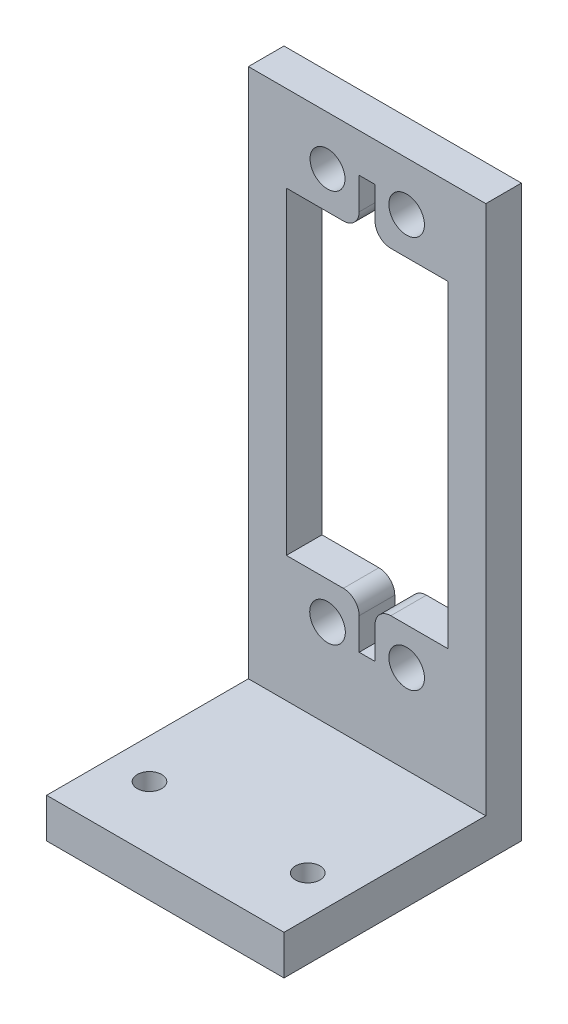
SolidWorks part; units mm, degrees
ref_plane "前视基准面" through (0, 0, 0) normal (0, 0, 1) x (1, 0, 0)
ref_plane "上视基准面" through (0, 0, 0) normal (0, 1, 0) x (1, 0, 0)
ref_plane "右视基准面" through (0, 0, 0) normal (1, 0, 0) x (0, 0, -1)
sketch "草图1" plane through (0, 0, 0) normal (0, 0, 1) x (1, 0, 0)
  line L1 (10.2, -20.1) -> (-10.2, -20.1)
  line L2 (10.2, -20.1) -> (10.2, 20.1)
  line L3 (10.2, 20.1) -> (-10.2, 20.1)
  line L4 (-10.2, -20.1) -> (-10.2, 20.1)
  line L5 (10.2, -20.1) -> (-10.2, 20.1) construction
  line L6 (10.2, 20.1) -> (-10.2, -20.1) construction
  line L7 (15, -31) -> (-15, -31)
  line L8 (15, -31) -> (15, 31)
  line L9 (15, 31) -> (-15, 31)
  line L10 (-15, -31) -> (-15, 31)
  line L11 (15, -31) -> (-15, 31) construction
  line L12 (15, 31) -> (-15, -31) construction
  point P0 (0, 0)
  point P5 (0, 0)
  dimension "D1" = 20.4
  dimension "D2" = 40.2
  dimension "D3" = 30
  dimension "D4" = 62
extrude "凸台-拉伸1" add sketch "草图1" along normal blind 4.5
sketch "草图3" plane through (0, 0, 0) normal (0, 0, -1) x (-1, 0, 0)
  circle A0 centre (-5, -24.8) radius 2.25
  circle A1 centre (5, -24.8) radius 2.25
  circle A2 centre (-5, 24.8) radius 2.25
  circle A3 centre (5, 24.8) radius 2.2065
extrude "切除-拉伸1" cut sketch "草图3" against normal through all
sketch "草图4" plane through (0, 31, 0) normal (0, 1, 0) x (1, 0, 0)
  line L4 (15, 0) -> (-15, 0)
  line L5 (-15, 0) -> (-15, -4.5)
  line L6 (-15, -4.5) -> (15, -4.5)
  line L7 (15, -4.5) -> (15, 0)
  line L8 (15, 0) -> (-15, 0)
  line L9 (-15, 0) -> (-15, -4.5)
  line L10 (-15, -4.5) -> (15, -4.5)
  line L11 (15, -4.5) -> (15, 0)
  dimension "D1" = 0
sketch "草图5" plane through (0, -31, 0) normal (0, -1, 0) x (1, 0, 0)
  line L4 (-15, 0) -> (15, 0)
  line L5 (15, 0) -> (15, 4.5)
  line L6 (15, 4.5) -> (-15, 4.5)
  line L7 (-15, 4.5) -> (-15, 0)
  line L8 (-15, 0) -> (15, 0)
  line L9 (15, 0) -> (15, 4.5)
  line L10 (15, 4.5) -> (-15, 4.5)
  line L11 (-15, 4.5) -> (-15, 0)
  dimension "D1" = 0
extrude "凸台-拉伸3" add sketch "草图5" along normal blind 5
sketch "草图6" plane through (0, -36, 0) normal (0, -1, 0) x (1, 0, 0)
  line L0 (-15, 4.5) -> (-15, 0) construction
  line L1 (15, 0) -> (-15, 0)
  line L2 (15, 0) -> (15, 30)
  line L3 (15, 30) -> (-15, 30)
  line L4 (-15, 0) -> (-15, 30)
  dimension "D1" = 30
extrude "凸台-拉伸4" add sketch "草图6" along normal blind 5
sketch "草图7" plane through (0, -41, 0) normal (0, -1, 0) x (1, 0, 0)
  line L0 (0, 30) -> (0, 22) construction
  line L1 (15, 30) -> (-15, 30) construction
  line L2 (0, 22) -> (10, 22) construction
  circle A0 centre (10, 22) radius 1.55
  circle A1 centre (-10, 22) radius 1.55
  dimension "D1" = 8
  dimension "D3" = 3.1
  dimension "D2" = 10
extrude "切除-拉伸2" cut sketch "草图7" against normal through all
sketch "草图8" plane through (0, 0, 4.5) normal (0, 0, 1) x (1, 0, 0)
  line L0 (0, -20.1) -> (0, -26.5553) construction
  line L1 (-10.2, -20.1) -> (10.2, -20.1) construction
  line L2 (0, 0) -> (13.0244, 0) construction
  line L3 (1, 20.1) -> (-1, 26.1) construction
  line L4 (1, -26.1) -> (-1, -26.1)
  line L5 (1, -26.1) -> (1, -20.1)
  line L6 (1, -20.1) -> (-1, -20.1)
  line L7 (-1, -26.1) -> (-1, -20.1)
  line L8 (1, -26.1) -> (-1, -20.1) construction
  line L9 (1, -20.1) -> (-1, -26.1) construction
  line L10 (1, 26.1) -> (-1, 20.1) construction
  line L11 (0, 20.1) -> (0, 26.5553) construction
  line L12 (-1, 26.1) -> (-1, 20.1)
  line L13 (1, 20.1) -> (-1, 20.1)
  line L14 (1, 26.1) -> (1, 20.1)
  line L15 (1, 26.1) -> (-1, 26.1)
  point P7 (0, -23.1)
  point P18 (0, 23.1)
  dimension "D1" = 2
  dimension "D2" = 6
extrude "切除-拉伸3" cut sketch "草图8" against normal through all
fillet "圆角1" radius 2 4 edges at (1, 20.1, 2.25) (-1, 20.1, 2.25) (1, -20.1, 2.25) (-1, -20.1, 2.25)
